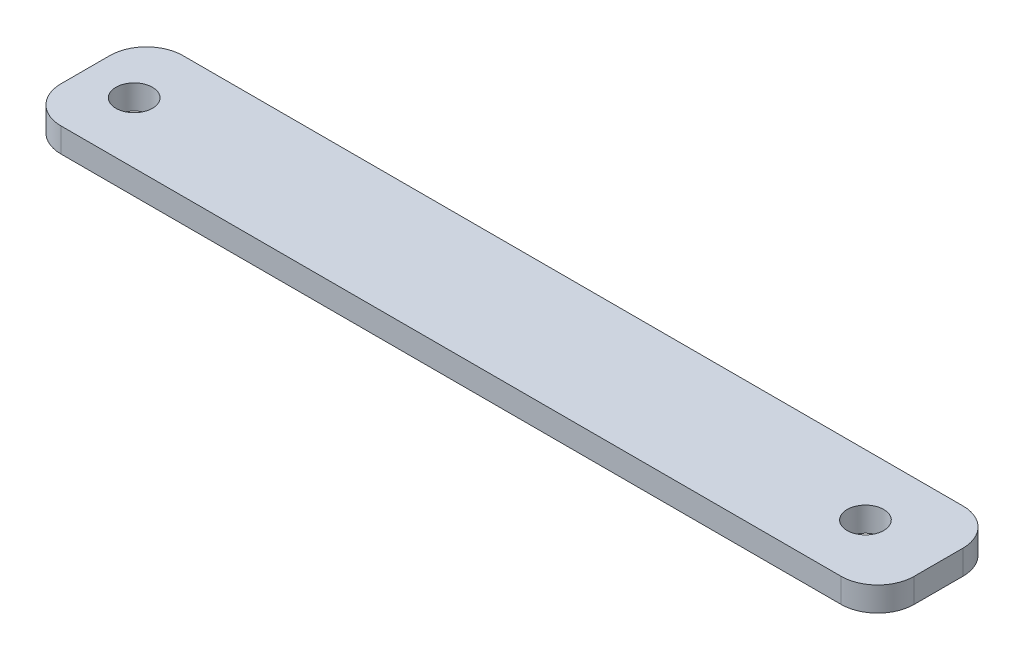
SolidWorks part; units mm, degrees
ref_plane "Front Plane" through (0, 0, 0) normal (0, 0, 1) x (1, 0, 0)
ref_plane "Top Plane" through (0, 0, 0) normal (0, 1, 0) x (1, 0, 0)
ref_plane "Right Plane" through (0, 0, 0) normal (1, 0, 0) x (0, 0, -1)
sketch "Sketch1" plane through (0, 0, 0) normal (0, 1, 0) x (1, 0, 0)
  line L1 (-35, 5) -> (35, 5)
  line L2 (-35, 5) -> (-35, -5)
  line L3 (-35, -5) -> (35, -5)
  line L4 (35, 5) -> (35, -5)
  line L5 (-35, 5) -> (35, -5) construction
  line L6 (-35, -5) -> (35, 5) construction
  point P0 (0, 0)
  dimension "D1" = 10
  dimension "D2" = 70
extrude "Boss-Extrude1" add sketch "Sketch1" along normal blind 2
sketch "Sketch2" plane through (0, 2, 0) normal (0, 1, 0) x (1, 0, 0)
  point P10 (26.3156, 0)
fillet "Fillet1" radius 3 4 edges at (35, 1, 5) (35, 1, -5) (-35, 1, 5) (-35, 1, -5)
hole_wizard "Ø3.0mm Dowel Hole1" positions "Sketch5" profile "Sketch6" hole size "Ø3.0" standard "ISO" end condition through all
sketch "Sketch5" plane through (0, 0, 0) normal (0, -1, 0) x (-1, 0, 0)
  line L1 (-35, -2) -> (-35, 2) construction
  line L3 (35, 0) -> (-35, 0) construction
  line L4 (35, 2) -> (35, -2) construction
  point P0 (-29, 0)
  point P2 (31, 0)
  dimension "D2" = 6
  dimension "=globalength1" = 60
sketch "Sketch6" plane through (29, 0, 0) normal (1, 0, 0) x (0, 0, -1)
  line L0 (0, 0) -> (0, 2)
  line L1 (0, 2) -> (1.5, 2)
  line L2 (1.5, 2) -> (1.5, 0)
  line L5 (1.5, 0) -> (0, 0)
  line L11 (0, -6.35) -> (0, 107.95) construction
  dimension "Thru Hole Dia." = 3
  dimension "Thru Hole Depth" = 2
equation "\"globalength1\"=55"
